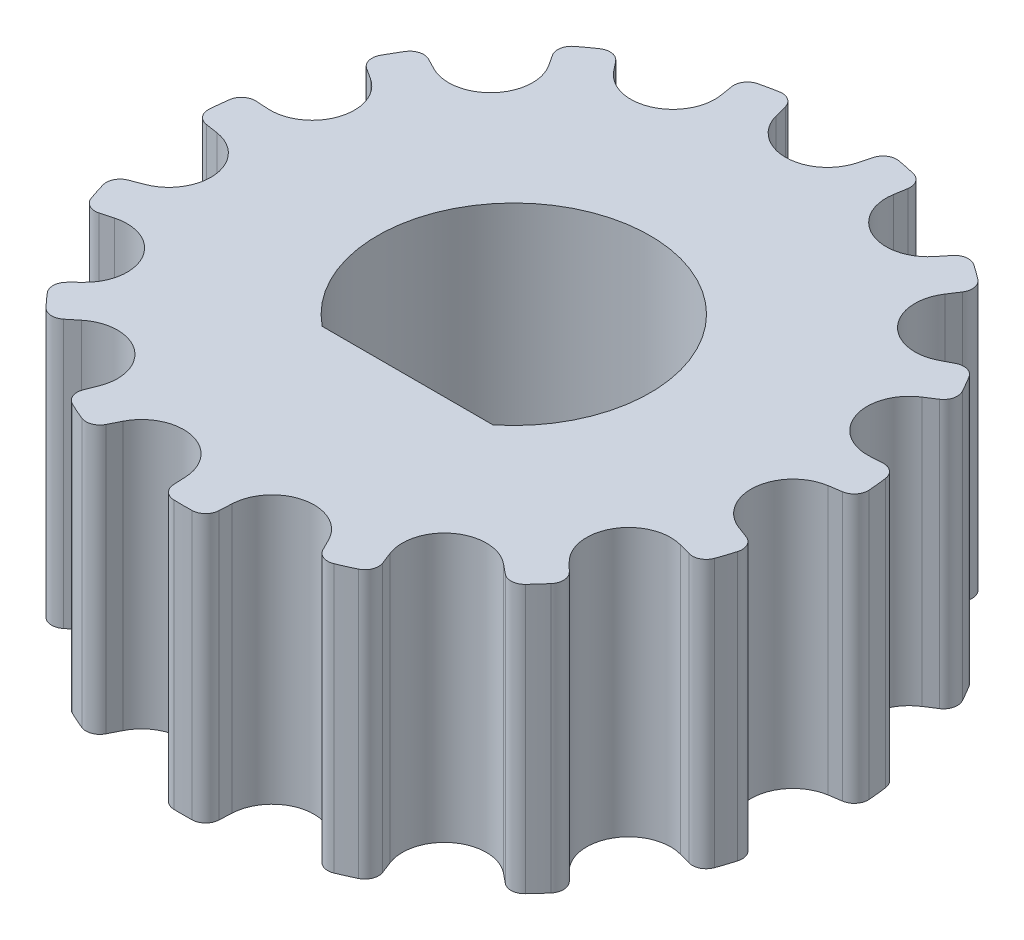
SolidWorks part; units mm, degrees
ref_plane "Front Plane" through (0, 0, 0) normal (0, 0, 1) x (1, 0, 0)
ref_plane "Top Plane" through (0, 0, 0) normal (0, 1, 0) x (1, 0, 0)
ref_plane "Right Plane" through (0, 0, 0) normal (1, 0, 0) x (0, 0, -1)
sketch "Sketch1" plane through (0, 0, 0) normal (0, 1, 0) x (1, 0, 0)
  circle A0 centre (0, 0) radius 7.162
  dimension "D1" = 14.3239
extrude "Boss-Extrude1" add sketch "Sketch1" along normal blind 5.8
sketch "Sketch2" plane through (0, 5.8, 0) normal (0, 1, 0) x (1, 0, 0)
  line L0 (0, 0) -> (0, 7.162) construction
  line L1 (-0.8799, 6.5598) -> (-0.95, 6.8255)
  line L2 (-2.913, 6.5428) -> (-2.913, 7.162)
  line L3 (-2.913, 7.162) -> (2.913, 7.162)
  line L4 (0.8799, 6.5598) -> (0.95, 6.8255)
  line L5 (2.913, 6.5428) -> (2.913, 7.162)
  circle A0 centre (0, 0) radius 7.162 construction
  arc A1 (0.8799, 6.5598) -> (-0.8799, 6.5598) centre (0, 6.792) cw
  arc A2 (-0.95, 6.8255) -> (-1.2943, 7.0441) centre (-1.2401, 6.749) ccw
  arc A4 (0.95, 6.8255) -> (1.2943, 7.0441) centre (1.2401, 6.749) cw
  arc A5 (-1.2943, 7.0441) -> (-2.913, 6.5428) centre (0, 0) ccw
  arc A6 (1.2943, 7.0441) -> (2.913, 6.5428) centre (0, 0) cw
  point P11 (0, 7.162)
  point P19 (0, 5.882)
  dimension "D3" = 0.3
  dimension "D5" = 0.91
  dimension "D2" = 0.95
  dimension "D4" = 1.28
  dimension "D6" = 24
extrude "Cut-Extrude1" cut sketch "Sketch2" against normal through all
pattern_circular "CirPattern1" count 15 over 360 about axis through (0, 5.8, 0) along (0, -1, 0) of "Cut-Extrude1"
sketch "Sketch3" plane through (0, 0, 0) normal (0, -1, 0) x (1, 0, 0)
  line L0 (1.8473, 2.3) -> (-1.8473, 2.3)
  arc A0 (-1.8473, 2.3) -> (1.8473, 2.3) centre (0, 0) ccw
  dimension "D1" = 5.9
  dimension "D2" = 2.3
extrude "Cut-Extrude2" cut sketch "Sketch3" against normal through all
sketch "Sketch5" plane through (0, 0, 0) normal (0, -1, 0) x (1, 0, 0)
  line L60 (5.4179, -3.8244) -> (5.6623, -3.9501)
  line L61 (6.252, -2.9286) -> (6.021, -2.7798)
  line L62 (6.505, -1.2901) -> (6.7794, -1.3055)
  line L63 (6.9027, -0.1325) -> (6.6311, -0.0906)
  line L64 (6.4674, 1.4673) -> (6.7243, 1.5648)
  line L65 (6.3598, 2.6865) -> (6.0946, 2.6144)
  line L66 (5.3115, 3.9709) -> (5.5065, 4.1645)
  line L67 (4.7173, 5.041) -> (4.5044, 4.8673)
  line L68 (3.2371, 5.788) -> (3.3366, 6.0442)
  line L69 (2.2591, 6.5239) -> (2.1352, 6.2786)
  line L70 (0.6031, 6.6042) -> (0.5897, 6.8787)
  line L71 (-0.5897, 6.8787) -> (-0.6031, 6.6042)
  line L72 (-2.1352, 6.2786) -> (-2.2591, 6.5239)
  line L73 (-3.3366, 6.0442) -> (-3.2371, 5.788)
  line L74 (-4.5044, 4.8673) -> (-4.7173, 5.041)
  line L75 (-5.5065, 4.1645) -> (-5.3115, 3.9709)
  line L76 (-6.0946, 2.6144) -> (-6.3598, 2.6865)
  line L77 (-6.7243, 1.5648) -> (-6.4674, 1.4673)
  line L78 (-6.6311, -0.0906) -> (-6.9027, -0.1325)
  line L79 (-6.7794, -1.3055) -> (-6.505, -1.2901)
  line L80 (-6.021, -2.7798) -> (-6.252, -2.9286)
  line L81 (-5.6623, -3.9501) -> (-5.4179, -3.8244)
  line L82 (-4.3698, -4.9885) -> (-4.5203, -5.2184)
  line L83 (-3.5661, -5.9117) -> (-3.394, -5.6974)
  line L84 (-1.963, -6.3345) -> (-2.007, -6.6058)
  line L85 (-0.8533, -6.851) -> (-0.7832, -6.5853)
  line L86 (0.7832, -6.5853) -> (0.8533, -6.851)
  line L87 (2.007, -6.6058) -> (1.963, -6.3345)
  line L88 (3.394, -5.6974) -> (3.5661, -5.9117)
  line L89 (4.5203, -5.2184) -> (4.3698, -4.9885)
  line L90 (5.4179, -3.8244) -> (5.6623, -3.9501)
  line L91 (6.252, -2.9286) -> (6.021, -2.7798)
  line L92 (6.505, -1.2901) -> (6.7794, -1.3055)
  line L93 (6.9027, -0.1325) -> (6.6311, -0.0906)
  line L94 (6.4674, 1.4673) -> (6.7243, 1.5648)
  line L95 (6.3598, 2.6865) -> (6.0946, 2.6144)
  line L96 (5.3115, 3.9709) -> (5.5065, 4.1645)
  line L97 (4.7173, 5.041) -> (4.5044, 4.8673)
  line L98 (3.2371, 5.788) -> (3.3366, 6.0442)
  line L99 (2.2591, 6.5239) -> (2.1352, 6.2786)
  line L100 (0.6031, 6.6042) -> (0.5897, 6.8787)
  line L101 (-0.5897, 6.8787) -> (-0.6031, 6.6042)
  line L102 (-2.1352, 6.2786) -> (-2.2591, 6.5239)
  line L103 (-3.3366, 6.0442) -> (-3.2371, 5.788)
  line L104 (-4.5044, 4.8673) -> (-4.7173, 5.041)
  line L105 (-5.5065, 4.1645) -> (-5.3115, 3.9709)
  line L106 (-6.0946, 2.6144) -> (-6.3598, 2.6865)
  line L107 (-6.7243, 1.5648) -> (-6.4674, 1.4673)
  line L108 (-6.6311, -0.0906) -> (-6.9027, -0.1325)
  line L109 (-6.7794, -1.3055) -> (-6.505, -1.2901)
  line L110 (-6.021, -2.7798) -> (-6.252, -2.9286)
  line L111 (-5.6623, -3.9501) -> (-5.4179, -3.8244)
  line L112 (-4.3698, -4.9885) -> (-4.5203, -5.2184)
  line L113 (-3.5661, -5.9117) -> (-3.394, -5.6974)
  line L114 (-1.963, -6.3345) -> (-2.007, -6.6058)
  line L115 (-0.8533, -6.851) -> (-0.7832, -6.5853)
  line L116 (0.7832, -6.5853) -> (0.8533, -6.851)
  line L117 (2.007, -6.6058) -> (1.963, -6.3345)
  line L118 (3.394, -5.6974) -> (3.5661, -5.9117)
  line L119 (4.5203, -5.2184) -> (4.3698, -4.9885)
  circle A60 centre (0, 0) radius 3.9038
  arc A120 (5.6623, -3.9501) -> (6.186, -3.8039) centre (5.8452, -3.5944) ccw
  arc A121 (6.186, -3.8039) -> (6.3873, -3.4553) centre (0, 0) ccw
  arc A122 (6.3873, -3.4553) -> (6.252, -2.9286) centre (6.0355, -3.2649) ccw
  arc A123 (6.505, -1.2901) -> (6.021, -2.7798) centre (6.4595, -2.0988) ccw
  arc A124 (6.7794, -1.3055) -> (7.1984, -0.959) centre (6.8019, -0.9062) ccw
  arc A125 (7.1984, -0.959) -> (7.2405, -0.5586) centre (0, 0) ccw
  arc A126 (7.2405, -0.5586) -> (6.9027, -0.1325) centre (6.8416, -0.5278) ccw
  arc A127 (6.4674, 1.4673) -> (6.6311, -0.0906) centre (6.7548, 0.71) ccw
  arc A128 (6.7243, 1.5648) -> (6.9661, 2.0518) centre (6.5824, 1.9387) ccw
  arc A129 (6.9661, 2.0518) -> (6.8417, 2.4347) centre (0, 0) ccw
  arc A130 (6.8417, 2.4347) -> (6.3598, 2.6865) centre (6.4648, 2.3006) ccw
  arc A131 (5.3115, 3.9709) -> (6.0946, 2.6144) centre (5.882, 3.396) ccw
  arc A132 (5.5065, 4.1645) -> (5.5293, 4.7077) centre (5.2248, 4.4484) ccw
  arc A133 (5.5293, 4.7077) -> (5.2599, 5.0069) centre (0, 0) ccw
  arc A134 (5.2599, 5.0069) -> (4.7173, 5.041) centre (4.9702, 4.7312) ccw
  arc A135 (3.2371, 5.788) -> (4.5044, 4.8673) centre (3.9922, 5.4948) ccw
  arc A136 (3.3366, 6.0442) -> (3.1365, 6.5497) centre (2.9637, 6.1889) ccw
  arc A137 (3.1365, 6.5497) -> (2.7687, 6.7135) centre (0, 0) ccw
  arc A138 (2.7687, 6.7135) -> (2.2591, 6.5239) centre (2.6162, 6.3437) ccw
  arc A139 (0.6031, 6.6042) -> (2.1352, 6.2786) centre (1.4121, 6.6436) ccw
  arc A140 (0.5897, 6.8787) -> (0.2013, 7.2592) centre (0.1902, 6.8593) ccw
  arc A141 (0.2013, 7.2592) -> (-0.2013, 7.2592) centre (0, 0) ccw
  arc A142 (-0.2013, 7.2592) -> (-0.5897, 6.8787) centre (-0.1902, 6.8593) ccw
  arc A143 (-2.1352, 6.2786) -> (-0.6031, 6.6042) centre (-1.4121, 6.6436) ccw
  arc A144 (-2.2591, 6.5239) -> (-2.7687, 6.7135) centre (-2.6162, 6.3437) ccw
  arc A145 (-2.7687, 6.7135) -> (-3.1365, 6.5497) centre (0, 0) ccw
  arc A146 (-3.1365, 6.5497) -> (-3.3366, 6.0442) centre (-2.9637, 6.1889) ccw
  arc A147 (-4.5044, 4.8673) -> (-3.2371, 5.788) centre (-3.9922, 5.4948) ccw
  arc A148 (-4.7173, 5.041) -> (-5.2599, 5.0069) centre (-4.9702, 4.7312) ccw
  arc A149 (-5.2599, 5.0069) -> (-5.5293, 4.7077) centre (0, 0) ccw
  arc A150 (-5.5293, 4.7077) -> (-5.5065, 4.1645) centre (-5.2248, 4.4484) ccw
  arc A151 (-6.0946, 2.6144) -> (-5.3115, 3.9709) centre (-5.882, 3.396) ccw
  arc A152 (-6.3598, 2.6865) -> (-6.8417, 2.4347) centre (-6.4648, 2.3006) ccw
  arc A153 (-6.8417, 2.4347) -> (-6.9661, 2.0518) centre (0, 0) ccw
  arc A154 (-6.9661, 2.0518) -> (-6.7243, 1.5648) centre (-6.5824, 1.9387) ccw
  arc A155 (-6.6311, -0.0906) -> (-6.4674, 1.4673) centre (-6.7548, 0.71) ccw
  arc A156 (-6.9027, -0.1325) -> (-7.2405, -0.5586) centre (-6.8416, -0.5278) ccw
  arc A157 (-7.2405, -0.5586) -> (-7.1984, -0.959) centre (0, 0) ccw
  arc A158 (-7.1984, -0.959) -> (-6.7794, -1.3055) centre (-6.8019, -0.9062) ccw
  arc A159 (-6.021, -2.7798) -> (-6.505, -1.2901) centre (-6.4595, -2.0988) ccw
  arc A160 (-6.252, -2.9286) -> (-6.3873, -3.4553) centre (-6.0355, -3.2649) ccw
  arc A161 (-6.3873, -3.4553) -> (-6.186, -3.8039) centre (0, 0) ccw
  arc A162 (-6.186, -3.8039) -> (-5.6623, -3.9501) centre (-5.8452, -3.5944) ccw
  arc A163 (-4.3698, -4.9885) -> (-5.4179, -3.8244) centre (-5.0474, -4.5447) ccw
  arc A164 (-4.5203, -5.2184) -> (-4.4297, -5.7545) centre (-4.1857, -5.4375) ccw
  arc A165 (-4.4297, -5.7545) -> (-4.104, -5.9911) centre (0, 0) ccw
  arc A166 (-4.104, -5.9911) -> (-3.5661, -5.9117) centre (-3.8779, -5.6611) ccw
  arc A167 (-1.963, -6.3345) -> (-3.394, -5.6974) centre (-2.7625, -6.2048) ccw
  arc A168 (-2.007, -6.6058) -> (-1.7062, -7.0587) centre (-1.6122, -6.6699) ccw
  arc A169 (-1.7062, -7.0587) -> (-1.3124, -7.1424) centre (0, 0) ccw
  arc A170 (-1.3124, -7.1424) -> (-0.8533, -6.851) centre (-1.2401, -6.749) ccw
  arc A171 (0.7832, -6.5853) -> (-0.7832, -6.5853) centre (0, -6.792) ccw
  arc A172 (0.8533, -6.851) -> (1.3124, -7.1424) centre (1.2401, -6.749) ccw
  arc A173 (1.3124, -7.1424) -> (1.7062, -7.0587) centre (0, 0) ccw
  arc A174 (1.7062, -7.0587) -> (2.007, -6.6058) centre (1.6122, -6.6699) ccw
  arc A175 (3.394, -5.6974) -> (1.963, -6.3345) centre (2.7625, -6.2048) ccw
  arc A176 (3.5661, -5.9117) -> (4.104, -5.9911) centre (3.8779, -5.6611) ccw
  arc A177 (4.104, -5.9911) -> (4.4297, -5.7545) centre (0, 0) ccw
  arc A178 (4.4297, -5.7545) -> (4.5203, -5.2184) centre (4.1857, -5.4375) ccw
  arc A179 (5.4179, -3.8244) -> (4.3698, -4.9885) centre (5.0474, -4.5447) ccw
  arc A180 (5.6623, -3.9501) -> (6.186, -3.8039) centre (5.8452, -3.5944) ccw
  arc A181 (6.186, -3.8039) -> (6.3873, -3.4553) centre (0, 0) ccw
  arc A182 (6.3873, -3.4553) -> (6.252, -2.9286) centre (6.0355, -3.2649) ccw
  arc A183 (6.505, -1.2901) -> (6.021, -2.7798) centre (6.4595, -2.0988) ccw
  arc A184 (6.7794, -1.3055) -> (7.1984, -0.959) centre (6.8019, -0.9062) ccw
  arc A185 (7.1984, -0.959) -> (7.2405, -0.5586) centre (0, 0) ccw
  arc A186 (7.2405, -0.5586) -> (6.9027, -0.1325) centre (6.8416, -0.5278) ccw
  arc A187 (6.4674, 1.4673) -> (6.6311, -0.0906) centre (6.7548, 0.71) ccw
  arc A188 (6.7243, 1.5648) -> (6.9661, 2.0518) centre (6.5824, 1.9387) ccw
  arc A189 (6.9661, 2.0518) -> (6.8417, 2.4347) centre (0, 0) ccw
  arc A190 (6.8417, 2.4347) -> (6.3598, 2.6865) centre (6.4648, 2.3006) ccw
  arc A191 (5.3115, 3.9709) -> (6.0946, 2.6144) centre (5.882, 3.396) ccw
  arc A192 (5.5065, 4.1645) -> (5.5293, 4.7077) centre (5.2248, 4.4484) ccw
  arc A193 (5.5293, 4.7077) -> (5.2599, 5.0069) centre (0, 0) ccw
  arc A194 (5.2599, 5.0069) -> (4.7173, 5.041) centre (4.9702, 4.7312) ccw
  arc A195 (3.2371, 5.788) -> (4.5044, 4.8673) centre (3.9922, 5.4948) ccw
  arc A196 (3.3366, 6.0442) -> (3.1365, 6.5497) centre (2.9637, 6.1889) ccw
  arc A197 (3.1365, 6.5497) -> (2.7687, 6.7135) centre (0, 0) ccw
  arc A198 (2.7687, 6.7135) -> (2.2591, 6.5239) centre (2.6162, 6.3437) ccw
  arc A199 (0.6031, 6.6042) -> (2.1352, 6.2786) centre (1.4121, 6.6436) ccw
  arc A200 (0.5897, 6.8787) -> (0.2013, 7.2592) centre (0.1902, 6.8593) ccw
  arc A201 (0.2013, 7.2592) -> (-0.2013, 7.2592) centre (0, 0) ccw
  arc A202 (-0.2013, 7.2592) -> (-0.5897, 6.8787) centre (-0.1902, 6.8593) ccw
  arc A203 (-2.1352, 6.2786) -> (-0.6031, 6.6042) centre (-1.4121, 6.6436) ccw
  arc A204 (-2.2591, 6.5239) -> (-2.7687, 6.7135) centre (-2.6162, 6.3437) ccw
  arc A205 (-2.7687, 6.7135) -> (-3.1365, 6.5497) centre (0, 0) ccw
  arc A206 (-3.1365, 6.5497) -> (-3.3366, 6.0442) centre (-2.9637, 6.1889) ccw
  arc A207 (-4.5044, 4.8673) -> (-3.2371, 5.788) centre (-3.9922, 5.4948) ccw
  arc A208 (-4.7173, 5.041) -> (-5.2599, 5.0069) centre (-4.9702, 4.7312) ccw
  arc A209 (-5.2599, 5.0069) -> (-5.5293, 4.7077) centre (0, 0) ccw
  arc A210 (-5.5293, 4.7077) -> (-5.5065, 4.1645) centre (-5.2248, 4.4484) ccw
  arc A211 (-6.0946, 2.6144) -> (-5.3115, 3.9709) centre (-5.882, 3.396) ccw
  arc A212 (-6.3598, 2.6865) -> (-6.8417, 2.4347) centre (-6.4648, 2.3006) ccw
  arc A213 (-6.8417, 2.4347) -> (-6.9661, 2.0518) centre (0, 0) ccw
  arc A214 (-6.9661, 2.0518) -> (-6.7243, 1.5648) centre (-6.5824, 1.9387) ccw
  arc A215 (-6.6311, -0.0906) -> (-6.4674, 1.4673) centre (-6.7548, 0.71) ccw
  arc A216 (-6.9027, -0.1325) -> (-7.2405, -0.5586) centre (-6.8416, -0.5278) ccw
  arc A217 (-7.2405, -0.5586) -> (-7.1984, -0.959) centre (0, 0) ccw
  arc A218 (-7.1984, -0.959) -> (-6.7794, -1.3055) centre (-6.8019, -0.9062) ccw
  arc A219 (-6.021, -2.7798) -> (-6.505, -1.2901) centre (-6.4595, -2.0988) ccw
  arc A220 (-6.252, -2.9286) -> (-6.3873, -3.4553) centre (-6.0355, -3.2649) ccw
  arc A221 (-6.3873, -3.4553) -> (-6.186, -3.8039) centre (0, 0) ccw
  arc A222 (-6.186, -3.8039) -> (-5.6623, -3.9501) centre (-5.8452, -3.5944) ccw
  arc A223 (-4.3698, -4.9885) -> (-5.4179, -3.8244) centre (-5.0474, -4.5447) ccw
  arc A224 (-4.5203, -5.2184) -> (-4.4297, -5.7545) centre (-4.1857, -5.4375) ccw
  arc A225 (-4.4297, -5.7545) -> (-4.104, -5.9911) centre (0, 0) ccw
  arc A226 (-4.104, -5.9911) -> (-3.5661, -5.9117) centre (-3.8779, -5.6611) ccw
  arc A227 (-1.963, -6.3345) -> (-3.394, -5.6974) centre (-2.7625, -6.2048) ccw
  arc A228 (-2.007, -6.6058) -> (-1.7062, -7.0587) centre (-1.6122, -6.6699) ccw
  arc A229 (-1.7062, -7.0587) -> (-1.3124, -7.1424) centre (0, 0) ccw
  arc A230 (-1.3124, -7.1424) -> (-0.8533, -6.851) centre (-1.2401, -6.749) ccw
  arc A231 (0.7832, -6.5853) -> (-0.7832, -6.5853) centre (0, -6.792) ccw
  arc A232 (0.8533, -6.851) -> (1.3124, -7.1424) centre (1.2401, -6.749) ccw
  arc A233 (1.3124, -7.1424) -> (1.7062, -7.0587) centre (0, 0) ccw
  arc A234 (1.7062, -7.0587) -> (2.007, -6.6058) centre (1.6122, -6.6699) ccw
  arc A235 (3.394, -5.6974) -> (1.963, -6.3345) centre (2.7625, -6.2048) ccw
  arc A236 (3.5661, -5.9117) -> (4.104, -5.9911) centre (3.8779, -5.6611) ccw
  arc A237 (4.104, -5.9911) -> (4.4297, -5.7545) centre (0, 0) ccw
  arc A238 (4.4297, -5.7545) -> (4.5203, -5.2184) centre (4.1857, -5.4375) ccw
  arc A239 (5.4179, -3.8244) -> (4.3698, -4.9885) centre (5.0474, -4.5447) ccw
  dimension "D1" = 0.1
extrude "Boss-Extrude2" [suppressed] add sketch "Sketch5" against normal up to surface (5.8 mm away) up to face at (0, 5.8, -0.325)
sketch "Sketch6" plane through (0, 5.8, 0) normal (0, 1, 0) x (1, 0, 0)
  circle A0 centre (0, -10) radius 2.5
  dimension "D1" = 5
  dimension "D2" = 10
extrude "Cut-Extrude3" [suppressed] cut sketch "Sketch6" against normal through all
equation "\"smallPulleyTeeth\"= 15"
equation "\"largePulleyTeeth\"= 30"
equation "\"eighthThick\"= 2.9mm"
equation "\"D1@Sketch1\"=3*\"smallPulleyTeeth\"/pi"
equation "\"D1@Boss-Extrude1\" = \"eighthThick\" * 2"
equation "\"D6@Sketch2\"=360/\"smallPulleyTeeth\""
equation "\"quarterThick\"=5.9mm"
equation "\"D1@CirPattern1\"=\"smallPulleyTeeth\""
equation "\"sixteenthThick\" = 1.7mm"
equation "\"OD\" = 145mm"
equation "\"puckAngle\" = 60.5deg"
equation "\"puckDiam\" = 76.5mm"
equation "\"axlePress\" = 5.9mm"
equation "\"press\" = 0.2mm"
equation "\"wheelClear\" = 0.3mm"
equation "\"10-32clear\" = 4.5mm"
equation "\"6-32clear\" = 3.3mm"
equation "\"8-32clear\" = 4.0mm"
equation "\"wheelHeight\" = 22mm"
equation "\"D1@Sketch3\"=\"axlePress\""
